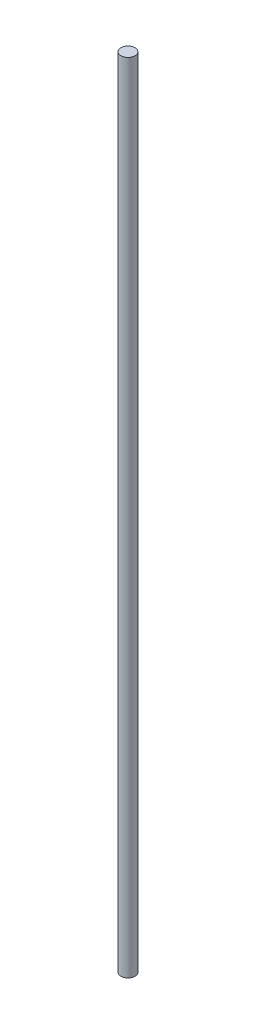
SolidWorks part; units mm, degrees
ref_plane "Front Plane" through (0, 0, 0) normal (0, 0, 1) x (1, 0, 0)
ref_plane "Top Plane" through (0, 0, 0) normal (0, 1, 0) x (1, 0, 0)
ref_plane "Right Plane" through (0, 0, 0) normal (1, 0, 0) x (0, 0, -1)
sketch "Sketch1" plane through (0, 0, 0) normal (0, 1, 0) x (1, 0, 0)
  circle A0 centre (0, 0) radius 4
  dimension "D1" = 8
extrude "Boss-Extrude1" add sketch "Sketch1" along normal blind 454.9
equation "\"d\"= 8"
equation "\"l\"= 454.9"
equation "\"D1@Boss-Extrude1\"=\"l\""
equation "\"D1@Sketch1\"=\"d\""
